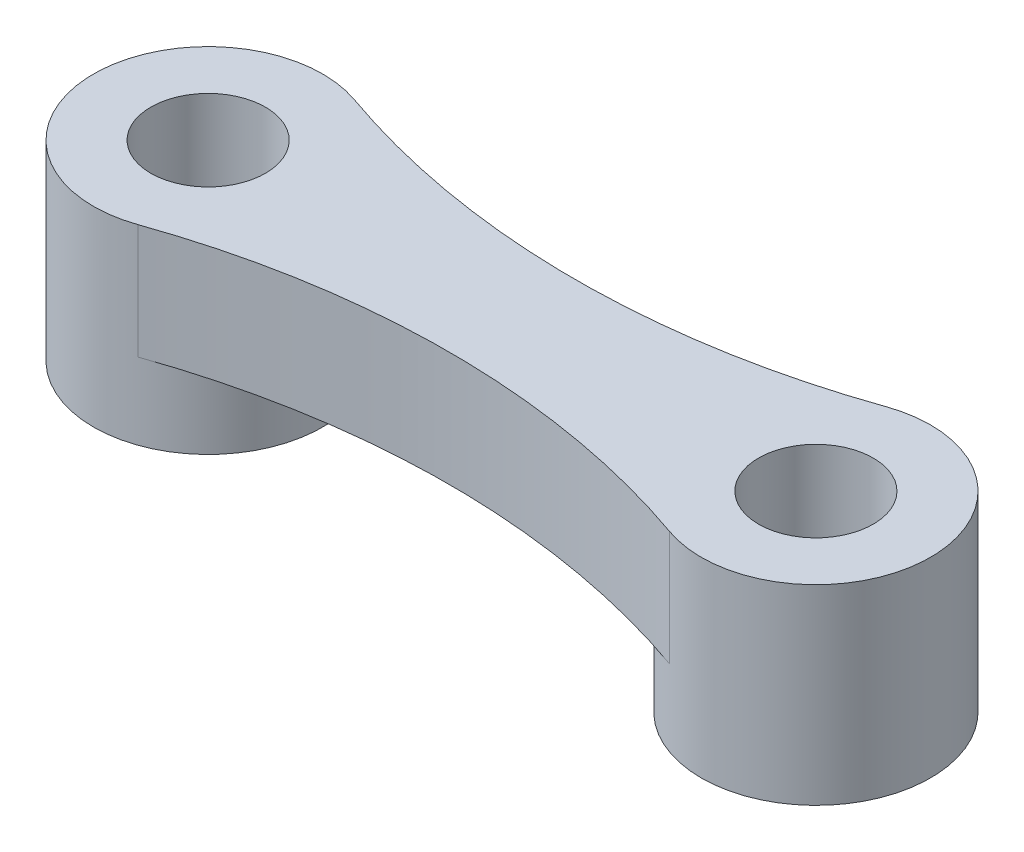
SolidWorks part; units mm, degrees
ref_plane "Front Plane" through (0, 0, 0) normal (0, 0, 1) x (1, 0, 0)
ref_plane "Top Plane" through (0, 0, 0) normal (0, 1, 0) x (1, 0, 0)
ref_plane "Right Plane" through (0, 0, 0) normal (1, 0, 0) x (0, 0, -1)
sketch "Sketch1" plane through (0, 0, 0) normal (0, 1, 0) x (1, 0, 0)
  line L0 (-7.95, 0) -> (7.95, 0) construction
  line L1 (-7.95, 3) -> (7.95, 3)
  line L2 (-7.95, -3) -> (7.95, -3)
  circle A0 centre (-7.95, 0) radius 1.5
  circle A1 centre (7.95, 0) radius 1.5
  arc A2 (-7.95, 3) -> (-7.95, -3) centre (-7.95, 0) ccw
  arc A3 (7.95, -3) -> (7.95, 3) centre (7.95, 0) ccw
  point P4 (0, 0)
  dimension "D2" = 3
  dimension "D3" = 3
  dimension "D4" = 6
  dimension "D5" = 6
  dimension "D1" = 15.9
extrude "Boss-Extrude1" add sketch "Sketch1" along normal blind 3
sketch "Sketch2" plane through (0, 3, 0) normal (0, 1, 0) x (1, 0, 0)
  line L0 (-7.95, 0) -> (7.95, 0) construction
  arc A0 (-6.9562, 2.8306) -> (-6.9562, -2.8306) centre (-7.95, 0) ccw
  arc A1 (6.9563, -2.8306) -> (6.9563, 2.8306) centre (7.95, 0) ccw
  arc A2 (-6.9562, 2.8306) -> (6.9563, 2.8306) centre (0, 22.645) ccw
  arc A3 (-7.95, 3) -> (-7.95, -3) centre (-7.95, 0) ccw construction
  arc A4 (7.95, -3) -> (7.95, 3) centre (7.95, 0) ccw construction
  arc A5 (-6.9562, -2.8306) -> (6.9563, -2.8306) centre (0, -22.645) cw
  dimension "D1" = 21
extrude "Cut-Extrude1" cut sketch "Sketch2" against normal through all flip side to cut
sketch "Sketch3" plane through (0, 3, 0) normal (0, 1, 0) x (1, 0, 0)
  circle A0 centre (-7.95, 0) radius 3
  circle A1 centre (7.95, 0) radius 3
  arc A2 (-6.9562, 2.8306) -> (-6.9562, -2.8306) centre (-7.95, 0) ccw construction
  arc A3 (6.9563, -2.8306) -> (6.9563, 2.8306) centre (7.95, 0) ccw construction
  circle A4 centre (7.95, 0) radius 1.5 construction
  circle A5 centre (-7.95, 0) radius 1.5 construction
  circle A6 centre (7.95, 0) radius 1.5
  circle A7 centre (-7.95, 0) radius 1.5
  circle M1 centre (-7.95, 0) radius 1.5
  circle M2 centre (7.95, 0) radius 1.5
  arc M3 (6.9563, -2.8306) -> (6.9563, 2.8306) centre (7.95, 0) ccw
  arc M5 (-6.9562, 2.8306) -> (-6.9562, -2.8306) centre (-7.95, 0) ccw
extrude "Boss-Extrude2" add sketch "Sketch3" against normal blind 2 from surface contours A0 M5 M1 | A1 M3 M2 region at (-5.5717, 3, 1.6857) region at (9.6357, 3, 2.3783) starting at face at (-7.95, 0, 1.5)
